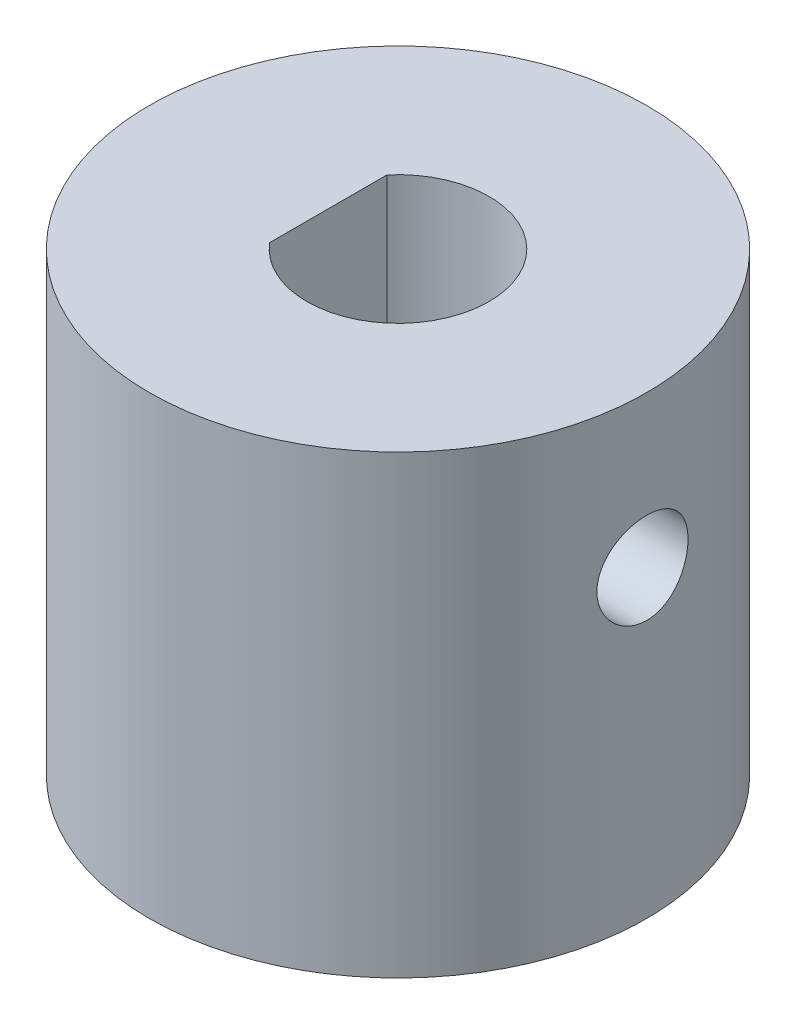
SolidWorks part; units mm, degrees
ref_plane "Front Plane" through (0, 0, 0) normal (0, 0, 1) x (1, 0, 0)
ref_plane "Top Plane" through (0, 0, 0) normal (0, 1, 0) x (1, 0, 0)
ref_plane "Right Plane" through (0, 0, 0) normal (1, 0, 0) x (0, 0, -1)
sketch "Sketch1" plane through (0, 0, 0) normal (0, 1, 0) x (1, 0, 0)
  circle A0 centre (0, 0) radius 8.189
extrude "Boss-Extrude1" add sketch "Sketch1" along normal blind 15
sketch "Sketch2" plane through (0, 15, 0) normal (0, 1, 0) x (1, 0, 0)
  circle A0 centre (0, 0) radius 3
extrude "Cut-Extrude1" cut sketch "Sketch2" against normal blind 30
sketch "Sketch4" plane through (0, 15, 0) normal (0, 1, 0) x (1, 0, 0)
  line L1 (-2.2951, -1.932) -> (-4.1343, -1.932)
  line L2 (-2.2951, -1.932) -> (-2.2951, 2.2587)
  line L3 (-2.2951, 2.2587) -> (-4.1343, 2.2587)
  line L4 (-4.1343, -1.932) -> (-4.1343, 2.2587)
  circle A0 centre (0, 0) radius 3 construction
extrude "Boss-Extrude2" add sketch "Sketch4" against normal blind 10
sketch "Sketch3" plane through (0, 0, 0) normal (1, 0, 0) x (0, 0, -1)
  circle A0 centre (0, 10) radius 1.5
  point P2 (0, 0)
extrude "Cut-Extrude2" cut sketch "Sketch3" against normal blind 10 and the other way blind 10
